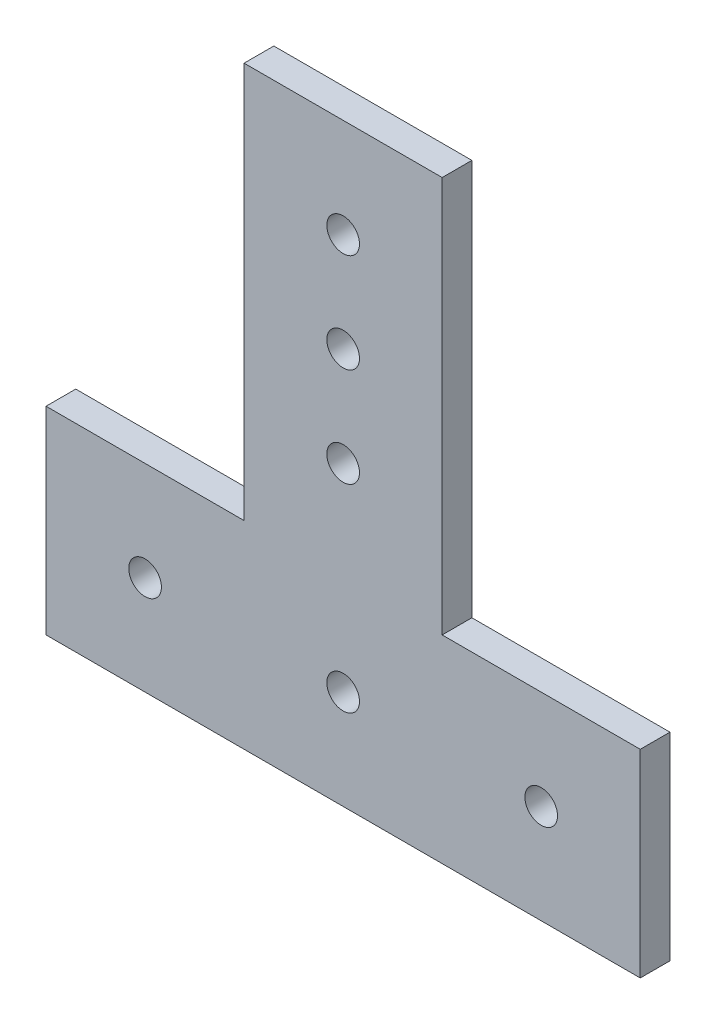
SolidWorks part; units mm, degrees
ref_plane "前视基准面" through (0, 0, 0) normal (0, 0, 1) x (1, 0, 0)
ref_plane "上视基准面" through (0, 0, 0) normal (0, 1, 0) x (1, 0, 0)
ref_plane "右视基准面" through (0, 0, 0) normal (1, 0, 0) x (0, 0, -1)
other "Configuration Table"
sketch "草图1" plane through (0, 0, 0) normal (0, 0, 1) x (1, 0, 0)
  line L0 (10, 10) -> (30, 10)
  line L1 (-30, -10) -> (30, -10)
  line L2 (-30, -10) -> (-30, 10)
  line L3 (-30, 10) -> (-10, 10)
  line L4 (30, -10) -> (30, 10)
  line L5 (-30, -10) -> (30, 10) construction
  line L6 (-30, 10) -> (30, -10) construction
  line L8 (-10, 10) -> (-10, 50)
  line L9 (-10, 50) -> (10, 50)
  line L10 (10, 10) -> (10, 50)
  circle A0 centre (0, 0) radius 1.65
  circle A1 centre (-20, 0) radius 1.65
  circle A2 centre (20, 0) radius 1.65
  circle A4 centre (0, 20) radius 1.65
  circle A5 centre (0, 30) radius 1.65
  circle A6 centre (0, 40) radius 1.65
  point P0 (0, 0)
  dimension "D9" = 10
  dimension "D6" = 3.3
  dimension "D10" = 3.3
  dimension "D11" = 3.3
  dimension "D1" = 20
  dimension "D2" = 20
  dimension "D3" = 60
  dimension "D4" = 20
  dimension "D5" = 40
  dimension "D7" = 20
  dimension "D8" = 20
  dimension "D12" = 10
  dimension "D13" = 10
extrude "凸台-拉伸1" add sketch "草图1" along normal blind 3
